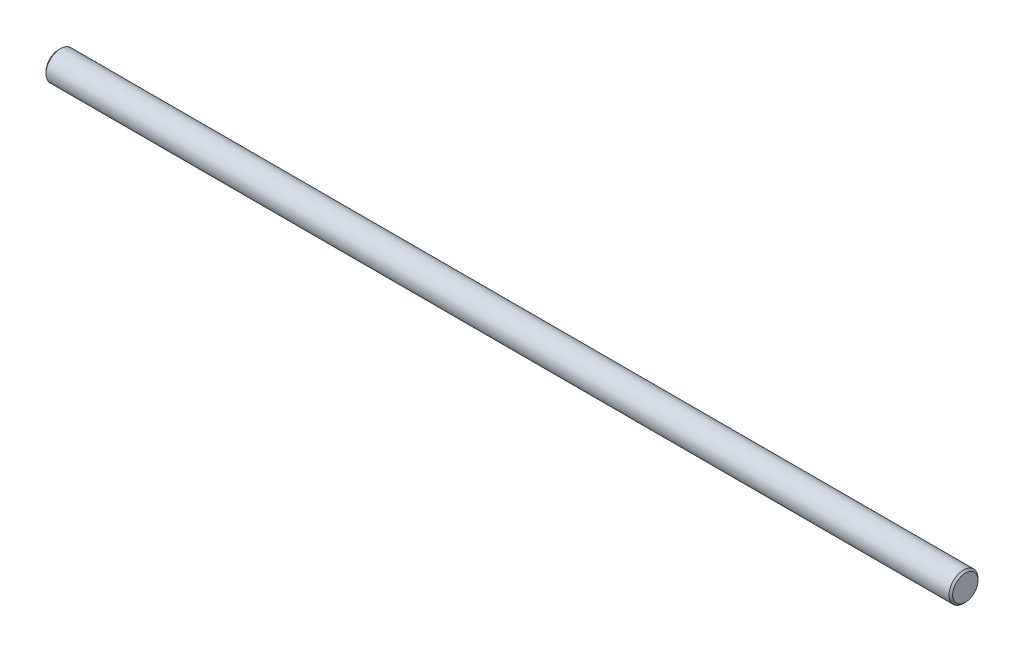
SolidWorks part; units mm, degrees
ref_plane "Front Plane" through (0, 0, 0) normal (0, 0, 1) x (1, 0, 0)
ref_plane "Top Plane" through (0, 0, 0) normal (0, 1, 0) x (1, 0, 0)
ref_plane "Right Plane" through (0, 0, 0) normal (1, 0, 0) x (0, 0, -1)
sketch "Sketch1" plane through (0, 0, 0) normal (0, 0, 1) x (1, 0, 0)
  line L0 (0, 0) -> (250, 0) construction
  line L1 (0, 0) -> (250, 0)
  line L2 (250, 0) -> (250, 4)
  line L3 (250, 4) -> (0, 4)
  line L4 (0, 4) -> (0, 0)
  dimension "L" = 250
  dimension "D" = 8
revolve "Revolve1" add sketch "Sketch1" angle 360 about L0
chamfer "Chamfer1" distance 0.5 angle 45 2 edges at (250, 0, 4) (0, 0, 4)
ref_plane "Plane1" through (0, 0, 4) normal (0, 0, 1) x (1, 0, 0)
ref_plane "Plane2" through (250, 0, 0) normal (1, 0, 0) x (0, 0, -1)
other "DeleteFace1" [suppressed]
chamfer "Chamfer2" [suppressed] distance 2 angle 45
ref_plane "Dim. KC" [suppressed] through (2, 0, 0) normal (1, 0, 0) x (0, 0, -1)
ref_plane "Plane3" [suppressed] through (2, 0, 0) normal (1, 0, 0) x (0, 0, -1)
ref_plane "Plane4" [suppressed] through (8, 0, 0) normal (1, 0, 0) x (0, 0, -1)
sketch "Sketch2" [suppressed] plane through (0, 0, 4) normal (0, 0, 1) x (1, 0, 0)
  line L0 (2, 0) -> (8, 0) construction
  line L1 (2, 1.5) -> (8, 1.5)
  line L2 (2, 1.5) -> (2, -1.5) construction
  line L3 (2, -1.5) -> (8, -1.5)
  line L4 (8, 1.5) -> (8, -1.5) construction
  line L5 (5, 1.5) -> (5, -1.5) construction
  line L6 (2, -4.4) -> (2, 4.4) construction
  line L7 (8, 1.5) -> (8, -1.5)
  line L8 (8, -4.4) -> (8, 4.4) construction
  line L9 (2, 1.5) -> (2, -1.5)
  line L12 (2, -4.4) -> (2, 4.4) construction
  dimension "A" = 6
  dimension "B_s" = 3
extrude "Boss-Extrude1" [suppressed] add sketch "Sketch2" against normal blind 1.8 separate body
fillet "Fillet1" [suppressed] type full round
fillet "Fillet2" [suppressed] type full round
sketch "Sketch3" [suppressed] plane through (0, 0, 4) normal (0, 0, 1) x (1, 0, 0)
  line L0 (9, 1.5) -> (9, -1.5) construction
  line L1 (6.5, 1.5) -> (11.5, 1.5)
  line L2 (6.5, 1.5) -> (6.5, -1.5)
  line L3 (6.5, -1.5) -> (11.5, -1.5)
  line L4 (11.5, 1.5) -> (11.5, -1.5)
  line L7 (6.5, 0) -> (11.5, 0) construction
  line L9 (10, 1.5) -> (10, -1.5) construction
  line L10 (8, 1.5) -> (8, -1.5) construction
  line L11 (2, 1.5) -> (8, 1.5) construction
  line L12 (2, -1.5) -> (8, -1.5) construction
  dimension "D1" = 1.5
  dimension "D2" = 2
  dimension "D3" = 1.5
extrude "Boss-Extrude2" [suppressed] add sketch "Sketch3" against normal blind 1.8
fillet "Fillet3" [suppressed] radius 0.1
other "DeleteFace2" [suppressed]
other "DeleteFace3" [suppressed]
combine bodies "Combine1" [suppressed] operation type subtract main body 101 bodies to subtract 146
ref_plane "KC_SEC1" [suppressed] through (5, 0, 0) normal (1, 0, 0) x (0, 0, -1)
ref_plane "KC_SEC2" [suppressed] through (9, 0, 0) normal (1, 0, 0) x (0, 0, -1)
ref_plane "Dim. WKC" [suppressed] through (2, 0, 0) normal (1, 0, 0) x (0, 0, -1)
ref_plane "Dim. K" [suppressed] through (20, 0, 0) normal (1, 0, 0) x (0, 0, -1)
ref_plane "Plane5" [suppressed] through (2, 0, 0) normal (1, 0, 0) x (0, 0, -1)
ref_plane "Plane6" [suppressed] through (20, 0, 0) normal (1, 0, 0) x (0, 0, -1)
sketch "Sketch4" [suppressed] plane through (0, 0, 4) normal (0, 0, 1) x (1, 0, 0)
  line L0 (2, 1.5) -> (2, -1.5)
  line L1 (2, 1.5) -> (8, 1.5)
  line L2 (2, 1.5) -> (2, -1.5) construction
  line L3 (2, -1.5) -> (8, -1.5)
  line L4 (8, 1.5) -> (8, -1.5)
  line L5 (2, -4.4) -> (2, 4.4) construction
  line L6 (2, -3.3) -> (2, 3.3) construction
  line L7 (8, 0) -> (2, 0) construction
  line L8 (5, 1.5) -> (5, -1.5) construction
  dimension "C" = 6
  dimension "B_s" = 3
extrude "Boss-Extrude3" [suppressed] add sketch "Sketch4" against normal blind 1.8 separate body
sketch "Sketch5" [suppressed] plane through (0, 0, 4) normal (0, 0, 1) x (1, 0, 0)
  line L0 (0, 0) -> (20, 0) construction
  line L2 (20, -3.3) -> (20, 3.3) construction
  line L4 (20, -3.3) -> (20, 3.3) construction
  line L5 (17, 1.5) -> (17, -1.5) construction
  line L9 (14, 1.5) -> (20, 1.5)
  line L10 (14, 1.5) -> (14, -1.5)
  line L11 (14, -1.5) -> (20, -1.5)
  line L12 (20, 1.5) -> (20, -1.5) construction
  line L13 (20, 1.5) -> (20, -1.5)
  dimension "B_s" = 3
  dimension "E" = 6
extrude "Boss-Extrude4" [suppressed] add sketch "Sketch5" against normal blind 1.8 separate body
sketch "Sketch6" [suppressed] plane through (0, 0, 4) normal (0, 0, 1) x (1, 0, 0)
  line L0 (2, 1.5) -> (8, 1.5) construction
  line L1 (6.5, 1.5) -> (11.5, 1.5)
  line L2 (6.5, 1.5) -> (6.5, -1.5)
  line L3 (6.5, -1.5) -> (11.5, -1.5)
  line L4 (11.5, 1.5) -> (11.5, -1.5)
  line L5 (2, -1.5) -> (8, -1.5) construction
  line L6 (8, 1.5) -> (8, -1.5) construction
  line L7 (9, 1.5) -> (9, -1.5) construction
  line L8 (10, 1.5) -> (10, -1.5) construction
  dimension "D1" = 1.5
  dimension "D2" = 2
  dimension "D3" = 1.5
extrude "Boss-Extrude5" [suppressed] add sketch "Sketch6" against normal blind 1.8
fillet "Fillet4" [suppressed] type full round
fillet "Fillet5" [suppressed] type full round
fillet "Fillet6" [suppressed] radius 0.1
fillet "Fillet7" [suppressed] type full round
fillet "Fillet8" [suppressed] type full round
fillet "Fillet9" [suppressed] radius 0.1
other "DeleteFace4" [suppressed]
other "DeleteFace5" [suppressed]
other "DeleteFace6" [suppressed]
other "DeleteFace7" [suppressed]
combine bodies "Combine2" [suppressed] operation type subtract main body 101 bodies to subtract 149 135
ref_plane "WKC_SEC1" [suppressed] through (5, 0, 0) normal (1, 0, 0) x (0, 0, -1)
ref_plane "WKC_SEC2" [suppressed] through (17, 0, 0) normal (1, 0, 0) x (0, 0, -1)
ref_plane "WKC_SEC3" [suppressed] through (9, 0, 0) normal (1, 0, 0) x (0, 0, -1)
ref_plane "Dim. KZ" [suppressed] through (2, 0, 0) normal (1, 0, 0) x (0, 0, -1)
ref_plane "Plane7" [suppressed] through (2, 0, 0) normal (1, 0, 0) x (0, 0, -1)
ref_plane "Plane8" [suppressed] through (8, 0, 0) normal (1, 0, 0) x (0, 0, -1)
sketch "Sketch7" [suppressed] plane through (0, 0, 4) normal (0, 0, 1) x (1, 0, 0)
  line L0 (0, 0) -> (8, 0) construction
  line L1 (2, 1.5) -> (8, 1.5)
  line L2 (2, 1.5) -> (2, -1.5) construction
  line L3 (2, -1.5) -> (8, -1.5)
  line L4 (8, 1.5) -> (8, -1.5) construction
  line L5 (2, -4.4) -> (2, 4.4) construction
  line L6 (2, -4.4) -> (2, 4.4) construction
  line L7 (2, 1.5) -> (2, -1.5)
  line L8 (8, 1.5) -> (8, -1.5)
  line L9 (8, -4.4) -> (8, 4.4) construction
  line L10 (5, 1.5) -> (5, -1.5) construction
  dimension "B_s" = 3
  dimension "Z" = 6
extrude "Boss-Extrude6" [suppressed] add sketch "Sketch7" against normal blind 1.8 separate body
fillet "Fillet10" [suppressed] type full round
fillet "Fillet11" [suppressed] type full round
sketch "Sketch8" [suppressed] plane through (0, 0, 4) normal (0, 0, 1) x (1, 0, 0)
  line L0 (1, 1.5) -> (1, -1.5) construction
  line L1 (-1.5, 1.5) -> (3.5, 1.5)
  line L2 (-1.5, 1.5) -> (-1.5, -1.5)
  line L3 (-1.5, -1.5) -> (3.5, -1.5)
  line L4 (3.5, 1.5) -> (3.5, -1.5)
  line L5 (2, 1.5) -> (2, -1.5) construction
  line L7 (-1.5, 0) -> (3.5, 0) construction
  line L9 (0, 1.5) -> (0, -1.5) construction
  line L10 (2, 1.5) -> (8, 1.5) construction
  line L11 (2, -1.5) -> (8, -1.5) construction
  dimension "D1" = 1.5
  dimension "D2" = 2
  dimension "D3" = 1.5
extrude "Boss-Extrude7" [suppressed] add sketch "Sketch8" against normal blind 1.8
fillet "Fillet12" [suppressed] radius 0.1
other "DeleteFace8" [suppressed]
other "DeleteFace9" [suppressed]
combine bodies "Combine3" [suppressed] operation type subtract main body 101 bodies to subtract 147
ref_plane "KZ_SEC1" [suppressed] through (5, 0, 0) normal (1, 0, 0) x (0, 0, -1)
ref_plane "KZ_SEC2" [suppressed] through (1, 0, 0) normal (1, 0, 0) x (0, 0, -1)
ref_plane "Dim. FC" [suppressed] through (1, 0, 0) normal (1, 0, 0) x (0, 0, -1)
sketch "Sketch9" [suppressed] plane through (0, 0, 0) normal (0, 1, 0) x (1, 0, 0)
  line L0 (0, 0) -> (2, 0) construction
  line L1 (1, -3) -> (2, -3)
  line L2 (1, -3) -> (1, -4)
  line L3 (1, -4) -> (2, -4)
  line L4 (2, -3) -> (2, -4)
  line L5 (1, -3.3) -> (1, 3.3) construction
  line L6 (1.5, -4) -> (1.5, -3) construction
  dimension "G" = 1
  dimension "H" = 1
  dimension "D" = 8
extrude "Cut-Extrude1" [suppressed] cut sketch "Sketch9" against normal through all and the other way through all
ref_plane "FC_SEC" [suppressed] through (1.5, 0, 0) normal (1, 0, 0) x (0, 0, -1)
ref_plane "Dim. WFC" [suppressed] through (1, 0, 0) normal (1, 0, 0) x (0, 0, -1)
ref_plane "Dim. W" [suppressed] through (19, 0, 0) normal (1, 0, 0) x (0, 0, -1)
sketch "Sketch10" [suppressed] plane through (0, 0, 0) normal (0, 1, 0) x (1, 0, 0)
  line L0 (0, 0) -> (19, 0) construction
  line L1 (1, -4) -> (2, -4)
  line L2 (1, -4) -> (1, -3)
  line L3 (1, -3) -> (2, -3)
  line L4 (2, -4) -> (2, -3)
  line L5 (1.5, -3) -> (1.5, -4) construction
  line L6 (19, -4) -> (18, -4)
  line L7 (19, -4) -> (19, -3)
  line L8 (19, -3) -> (18, -3)
  line L9 (18, -4) -> (18, -3)
  line L10 (1, -3.3) -> (1, 3.3) construction
  line L11 (19, -3.3) -> (19, 3.3) construction
  line L12 (18.5, -3) -> (18.5, -4) construction
  dimension "J" = 1
  dimension "V" = 1
  dimension "H" = 1
  dimension "D" = 8
  dimension "H_s_R" = 1
extrude "Cut-Extrude2" [suppressed] cut sketch "Sketch10" against normal through all and the other way through all
ref_plane "WFC_SEC1" [suppressed] through (1.5, 0, 0) normal (1, 0, 0) x (0, 0, -1)
ref_plane "WFC_SEC2" [suppressed] through (18.5, 0, 0) normal (1, 0, 0) x (0, 0, -1)
ref_plane "Dim. SFC" [suppressed] through (1, 0, 0) normal (1, 0, 0) x (0, 0, -1)
sketch "Sketch11" [suppressed] plane through (0, 0, 0) normal (0, 1, 0) x (1, 0, 0)
  line L0 (0, 0) -> (2, 0) construction
  line L1 (1, -4) -> (2, -4)
  line L2 (1, -4) -> (1, -3)
  line L3 (1, -3) -> (2, -3)
  line L4 (2, -4) -> (2, -3)
  line L5 (1, -3.3) -> (1, 3.3) construction
  line L6 (1.5, -3) -> (1.5, -4) construction
  dimension "SG" = 1
  dimension "H" = 1
  dimension "D" = 8
extrude "Cut-Extrude3" [suppressed] cut sketch "Sketch11" against normal through all and the other way through all
pattern_circular "CirPattern1" [suppressed] count 2 every 120 of bodies 119
ref_plane "Plane9" [suppressed] through (0, 0, 0) normal (0, -0.5, 0.866) x (1, 0, 0)
sketch "Sketch12" [suppressed] plane through (0, 0, 0) normal (0, -0.5, 0.866) x (1, 0, 0)
  line L0 (0, 0) -> (2, 0) construction
  line L2 (1, -3) -> (2, -3)
  line L3 (1, -3) -> (1, -4)
  line L4 (1, -4) -> (2, -4)
  line L5 (2, -3) -> (2, -4)
  line L6 (1, -3.3) -> (1, 3.3) construction
  dimension "D" = 8
  dimension "SG" = 1
  dimension "H" = 1
ref_plane "SFC_SEC" [suppressed] through (1.5, 0, 0) normal (1, 0, 0) x (0, 0, -1)
sketch "Sketch13" [suppressed] plane through (1.5, 0, 0) normal (1, 0, 0) x (0, 0, -1)
  line L0 (-4, 0) -> (-3, 0) construction
  line L1 (-3, 0) -> (-4, 0) construction
  line L2 (2, -3.4641) -> (1.5, -2.5981) construction
  line L3 (1.5, -2.5981) -> (2, -3.4641) construction
  line L4 (1.5, -2.5981) -> (2, -3.4641) construction
  dimension "ANG" = 120
sketch "Sketch14" [suppressed] plane through (0, 0, 0) normal (0, 1, 0) x (1, 0, 0)
  line L0 (0, 0) -> (20, 0) construction
  line L1 (1.5, 4) -> (1.5, 3.5) construction
  line L2 (0, 3.5) -> (3, 3.5)
  line L3 (0, 3.5) -> (0, 4)
  line L4 (0, 4) -> (3, 4)
  line L5 (3, 3.5) -> (3, 4)
  line L6 (17, 3.5) -> (20, 3.5)
  line L7 (17, 3.5) -> (17, 4)
  line L8 (17, 4) -> (20, 4)
  line L9 (20, 3.5) -> (20, 4)
  line L10 (0, -4) -> (3, -4)
  line L11 (0, -4) -> (0, -3.5)
  line L12 (0, -3.5) -> (3, -3.5)
  line L13 (3, -4) -> (3, -3.5)
  line L14 (17, -4) -> (20, -4)
  line L15 (17, -4) -> (17, -3.5)
  line L16 (17, -3.5) -> (20, -3.5)
  line L17 (20, -4) -> (20, -3.5)
  line L18 (1.5, -3.5) -> (1.5, -4) construction
  line L19 (18.5, 4) -> (18.5, 3.5) construction
  line L20 (18.5, -3.5) -> (18.5, -4) construction
  dimension "D" = 8
  dimension "W_1" = 7
  dimension "KWC" = 3
  dimension "KWC_L1" = 3
  dimension "KWC_R1" = 3
  dimension "KWC_R2" = 3
  dimension "W_1_R" = 7
extrude "Cut-Extrude4" [suppressed] cut sketch "Sketch14" against normal through all and the other way through all
ref_plane "KWC_SEC1" [suppressed] through (1.5, 0, 0) normal (1, 0, 0) x (0, 0, -1)
ref_plane "KWC_SEC2" [suppressed] through (18.5, 0, 0) normal (1, 0, 0) x (0, 0, -1)
sketch "Sketch15" [suppressed] plane through (0, 0, 0) normal (0, 1, 0) x (1, 0, 0)
  line L0 (0, 0) -> (20, 0) construction
  line L1 (1.5, -3) -> (1.5, -4) construction
  line L2 (0, 3) -> (3, 3)
  line L3 (0, 3) -> (0, 4)
  line L4 (0, 4) -> (3, 4)
  line L5 (3, 3) -> (3, 4)
  line L6 (17, 3) -> (20, 3)
  line L7 (17, 3) -> (17, 4)
  line L8 (17, 4) -> (20, 4)
  line L9 (20, 3) -> (20, 4)
  line L10 (0, -4) -> (3, -4)
  line L11 (0, -4) -> (0, -3)
  line L12 (0, -3) -> (3, -3)
  line L13 (3, -4) -> (3, -3)
  line L14 (17, -4) -> (20, -4)
  line L15 (17, -4) -> (17, -3)
  line L16 (17, -3) -> (20, -3)
  line L17 (20, -4) -> (20, -3)
  line L18 (18.5, -3) -> (18.5, -4) construction
  dimension "D" = 8
  dimension "KWC_L1" = 3
  dimension "KWC_R1" = 3
  dimension "WC" = 6
  dimension "KWC" = 3
  dimension "KWC_R2" = 3
  dimension "WC_R" = 6
extrude "Cut-Extrude5" [suppressed] cut sketch "Sketch15" against normal through all and the other way through all
ref_plane "WC_SEC1" [suppressed] through (1.5, 0, 0) normal (1, 0, 0) x (0, 0, -1)
ref_plane "WC_SEC2" [suppressed] through (18.5, 0, 0) normal (1, 0, 0) x (0, 0, -1)
sketch "Sketch16" [suppressed] plane through (0, 0, 0) normal (0, 0, 1) x (1, 0, 0)
  line L0 (20, 4) -> (0, 4) construction
  line L1 (1.1, 3.5) -> (2, 3.5)
  line L2 (1.1, 3.5) -> (1.1, 4)
  line L3 (1.1, 4) -> (2, 4)
  line L4 (2, 3.5) -> (2, 4)
  line L5 (0, 0) -> (2, 0) construction
  line L6 (0, 4) -> (0, 0) construction
  dimension "D_s_1" = 7
  dimension "M_s" = 0.9
  dimension "TA" = 2
revolve "Cut-Revolve1" [suppressed] cut sketch "Sketch16" angle 360 about L5
sketch "Sketch17" [suppressed] plane through (0, 0, 0) normal (0, 0, 1) x (1, 0, 0)
  line L1 (18, 3.5) -> (18.9, 3.5)
  line L2 (18, 3.5) -> (18, 4)
  line L3 (18, 4) -> (18.9, 4)
  line L4 (18.9, 3.5) -> (18.9, 4)
  line L5 (0, 0) -> (20, 0) construction
  line L7 (20, -3.3) -> (20, 3.3) construction
  dimension "D_s_1" = 7
  dimension "M_s" = 0.9
  dimension "D" = 8
  dimension "TB" = 2
revolve "Cut-Revolve2" [suppressed] cut sketch "Sketch17" angle 360 about L5
sketch "Sketch18" [suppressed] plane through (0, 0, 0) normal (0, 0, 1) x (1, 0, 0)
  line L0 (0, 0) -> (20, 0) construction
  line L1 (0, 4) -> (0, -4) construction
  line L3 (1, 4) -> (5, 4)
  line L4 (1, 4) -> (1, 3.5)
  line L5 (1, 3.5) -> (5, 3.5)
  line L6 (5, 4) -> (5, 3.5)
  line L7 (20, 4) -> (0, 4) construction
  line L8 (20, -3.3) -> (20, 3.3) construction
  dimension "D_s_2" = 7
  dimension "UC" = 1
  dimension "L1_s" = 4
revolve "Cut-Revolve3" [suppressed] cut sketch "Sketch18" angle 360 about L0
ref_plane "Dim. SC" [suppressed] through (2, 0, 0) normal (1, 0, 0) x (0, 0, -1)
sketch "Sketch19" [suppressed] plane through (0, 0, 0) normal (0, 1, 0) x (1, 0, 0)
  line L0 (20, -3.3) -> (20, 3.3) construction
  line L1 (2, -3.5) -> (10, -3.5)
  line L2 (2, -3.5) -> (2, -4)
  line L3 (2, -4) -> (10, -4)
  line L4 (10, -3.5) -> (10, -4)
  line L5 (2, 4) -> (10, 4)
  line L6 (2, 4) -> (2, 3.5)
  line L7 (2, 3.5) -> (10, 3.5)
  line L8 (10, 4) -> (10, 3.5)
  line L9 (6, 4) -> (6, 3.5) construction
  line L10 (6, -3.5) -> (6, -4) construction
  line L12 (0, 0) -> (20, 0) construction
  line L14 (2, -3.3) -> (2, 3.3) construction
  dimension "W_2" = 7
  dimension "L2_s" = 8
  dimension "D" = 8
  dimension "L2_s_L1" = 8
extrude "Cut-Extrude6" [suppressed] cut sketch "Sketch19" against normal through all and the other way through all
ref_plane "SC_SEC" [suppressed] through (6, 0, 0) normal (1, 0, 0) x (0, 0, -1)
equation "\"Plane dim\"= \"D@Sketch1\" * 0.5"
equation "\"D1@Plane3\"= if ( \"KC@Dim. KC\" < 1 , 0 , \"KC@Dim. KC\" )"
equation "\"D1@Plane4\" = if ( \"KC@Dim. KC\" > \"L@Sketch1\" - \"A@Sketch2\" - 1 , \"L@Sketch1\" , \"KC@Dim. KC\" + \"A@Sketch2\" )"
equation "\"D1@Plane5\"=if ( \"WKC@Dim. WKC\" < 1 , 0 , \"WKC@Dim. WKC\" )"
equation "\"D1@Plane6\"=if ( \"K@Dim. K\" < 1 , 0 , \"K@Dim. K\" )"
equation "\"D1@Plane7\"=if ( \"KZ@Dim. KZ\" < 1 , 0 , \"KZ@Dim. KZ\" )"
equation "\"D1@Plane8\"=if ( \"KZ@Dim. KZ\" > \"L@Sketch1\" - \"Z@Sketch7\" - 1 , \"L@Sketch1\", \"KZ@Dim. KZ\" + \"Z@Sketch7\" )"
equation "\"D1@Sketch3\"=\"B_s@Sketch2\"/2"
equation "\"D3@Sketch3\"=\"B_s@Sketch2\"/2"
equation "\"D1@Sketch8\"=\"B_s@Sketch7\"/2"
equation "\"D3@Sketch8\"=\"B_s@Sketch7\"/2"
equation "\"D1@Sketch6\"=\"B_s@Sketch4\"/2"
equation "\"D3@Sketch6\"=\"B_s@Sketch4\"/2"
equation "\"D@Sketch12\" = \"D@Sketch11\""
equation "\"SG@Sketch12\" = \"SG@Sketch11\""
equation "\"H@Sketch12\"= \"H@Sketch11\""
